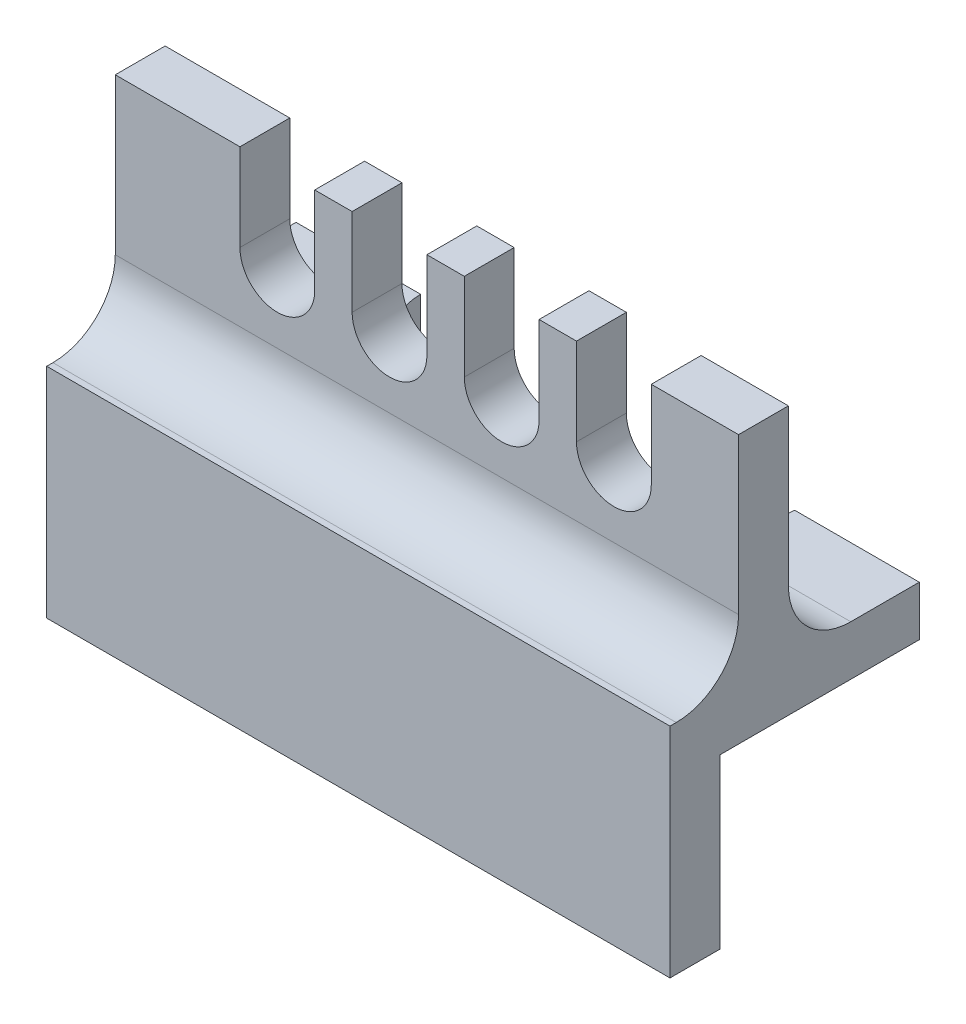
SolidWorks part; units mm, degrees
ref_plane "Front Plane" through (0, 0, 0) normal (0, 0, 1) x (1, 0, 0)
ref_plane "Top Plane" through (0, 0, 0) normal (0, 1, 0) x (1, 0, 0)
ref_plane "Right Plane" through (0, 0, 0) normal (1, 0, 0) x (0, 0, -1)
sketch "Sketch1" plane through (0, 0, 0) normal (1, 0, 0) x (0, 0, -1)
  line L0 (0, 0) -> (0, 35)
  line L1 (0, 35) -> (11, 35)
  line L2 (11, 35) -> (11, 70)
  line L3 (11, 70) -> (19, 70)
  line L4 (19, 70) -> (19, 35)
  line L5 (19, 35) -> (40, 35)
  line L6 (40, 35) -> (40, 27)
  line L7 (40, 27) -> (8, 27)
  line L8 (8, 27) -> (8, 0)
  line L9 (8, 0) -> (0, 0)
  dimension "D1" = 8
  dimension "D2" = 27
  dimension "D3" = 8
  dimension "D4" = 35
  dimension "D5" = 70
  dimension "D6" = 21
  dimension "D7" = 40
extrude "Boss-Extrude1" add sketch "Sketch1" against normal blind 100
fillet "Fillet1" radius 10 2 edges at (-50, 35, -11) (-50, 35, -19)
sketch "Sketch4" plane through (0, 0, -40) normal (0, 0, -1) x (-1, 0, 0)
  line L0 (20, 35) -> (80, 35)
  line L1 (100, 35) -> (0, 35) construction
  line L2 (80, 35) -> (80, 27)
  line L3 (100, 27) -> (0, 27) construction
  line L4 (80, 27) -> (20, 27)
  line L5 (20, 27) -> (20, 35)
  line L6 (100, 27) -> (100, 35) construction
  dimension "D1" = 20
  dimension "D2" = 60
extrude "Cut-Extrude1" cut sketch "Sketch4" against normal blind 10
fillet "Fillet2" radius 10 2 edges at (-20, 31, -30) (-80, 31, -30)
sketch "Sketch5" plane through (0, 0, -19) normal (0, 0, -1) x (-1, 0, 0)
  line L0 (0, 45) -> (0, 70) construction
  line L1 (100, 70) -> (0, 70) construction
  line L2 (14, 70) -> (14, 56)
  line L3 (14, 56) -> (26, 56)
  line L4 (26, 56) -> (26, 70)
  line L5 (26, 70) -> (14, 70)
  line L6 (32, 56) -> (44, 56)
  line L10 (44, 56) -> (44, 70)
  line L15 (68, 70) -> (68, 56)
  line L16 (68, 56) -> (80, 56)
  line L17 (80, 56) -> (80, 70)
  line L18 (80, 70) -> (68, 70)
  line L20 (32, 70) -> (32, 56)
  line L24 (44, 70) -> (32, 70)
  line L25 (50, 70) -> (50, 56)
  line L26 (50, 56) -> (62, 56)
  line L27 (62, 56) -> (62, 70)
  line L28 (62, 70) -> (50, 70)
  point P0 (20, 56)
  dimension "D1" = 20
  dimension "D2" = 12
  dimension "D3" = 6
  dimension "D4" = 12
  dimension "D5" = 6
  dimension "D6" = 12
  dimension "D7" = 14
  dimension "D8" = 14
  dimension "D9" = 14
  dimension "D10" = 6
  dimension "D11" = 12
  dimension "D12" = 14
extrude "Cut-Extrude2" cut sketch "Sketch5" against normal blind 10
sketch "Sketch6" plane through (0, 0, -19) normal (0, 0, -1) x (-1, 0, 0)
  line L0 (14, 58.5787) -> (14, 56)
  line L1 (14, 70) -> (14, 56) construction
  line L2 (26, 56) -> (26, 58.5787)
  line L3 (26, 56) -> (26, 70) construction
  line L4 (26, 58.5787) -> (14, 58.5787)
  line L5 (32, 56) -> (32, 58.5787)
  line L6 (32, 70) -> (32, 56) construction
  line L7 (32, 58.5787) -> (44, 58.5787)
  line L8 (44, 56) -> (44, 70) construction
  line L9 (44, 58.5787) -> (44, 56)
  line L10 (50, 56) -> (50, 58.5787)
  line L11 (50, 70) -> (50, 56) construction
  line L12 (50, 58.5787) -> (62, 58.5787)
  line L13 (62, 56) -> (62, 70) construction
  line L14 (62, 58.5787) -> (62, 56)
  line L15 (68, 56) -> (68, 58.5787)
  line L16 (68, 70) -> (68, 56) construction
  line L17 (68, 58.5787) -> (80, 58.5787)
  line L18 (80, 56) -> (80, 70) construction
  line L19 (80, 58.5787) -> (80, 56)
  arc A0 (14, 56) -> (26, 56) centre (20, 56) ccw
  arc A1 (44, 56) -> (32, 56) centre (38, 56) cw
  arc A2 (62, 56) -> (50, 56) centre (56, 56) cw
  arc A3 (80, 56) -> (68, 56) centre (74, 56) cw
extrude "Cut-Extrude3" cut sketch "Sketch6" against normal blind 10
